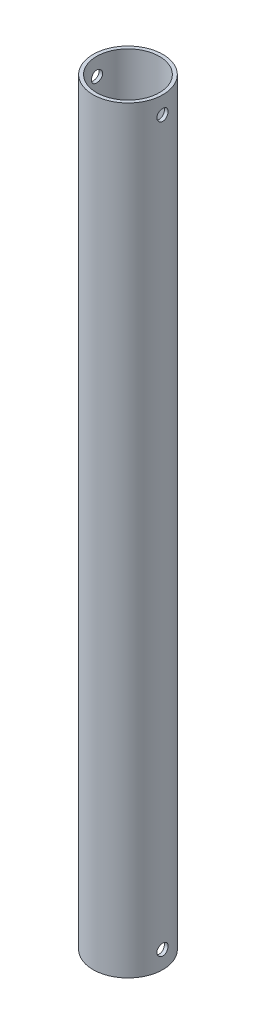
SolidWorks part; units mm, degrees
material "Toray T700"
ref_plane "Front" through (0, 0, 0) normal (0, 0, 1) x (1, 0, 0)
ref_plane "Top" through (0, 0, 0) normal (0, 1, 0) x (1, 0, 0)
ref_plane "Right" through (0, 0, 0) normal (1, 0, 0) x (0, 0, -1)
sketch "Sketch1" plane through (0, 0, 0) normal (0, 1, 0) x (1, 0, 0)
  line L5 (4.7969, 0) -> (-5.97, 0) construction
  circle A0 centre (0, 0) radius 10
  circle A1 centre (0, 0) radius 9
  dimension "D1" = 20
  dimension "D2" = 18
extrude "Boss-Extrude1" add sketch "Sketch1" along normal blind 217
ref_axis "Axis1" through (0, 217, 0) along (0, -1, 0)
ref_plane "Plane1" through (-10, 0, 0) normal (-1, 0, 0) x (0, 0, 1)
hole_wizard "M3 Clearance Hole1" positions "Sketch3" profile "Sketch2" hole size "M3" standard "DIN" end condition through all
sketch "Sketch3" plane through (-10, 0, 0) normal (-1, 0, 0) x (0, 0, 1)
  line L0 (-9, 0) -> (9, 0) construction
  line L1 (0, -50) -> (0, 50) construction
  point P0 (0, 5)
  dimension "D1" = 5
sketch "Sketch2" plane through (-10, 5, 0) normal (0, 1, 0) x (0, 0, 1)
  line L0 (0, 0) -> (0, 20)
  line L1 (0, 20) -> (1.6, 20)
  line L2 (1.6, 20) -> (1.6, 0)
  line L5 (1.6, 0) -> (0, 0)
  line L11 (0, -6.35) -> (0, 107.95) construction
  dimension "Thru Hole Dia." = 3.2
  dimension "Thru Hole Depth" = 20
ref_plane "Plane2" through (0, 108.5, 0) normal (0, 1, 0) x (1, 0, 0)
mirror "Mirror1" about plane through (0, 108.5, 0) normal (0, 1, 0) of "M3 Clearance Hole1"
